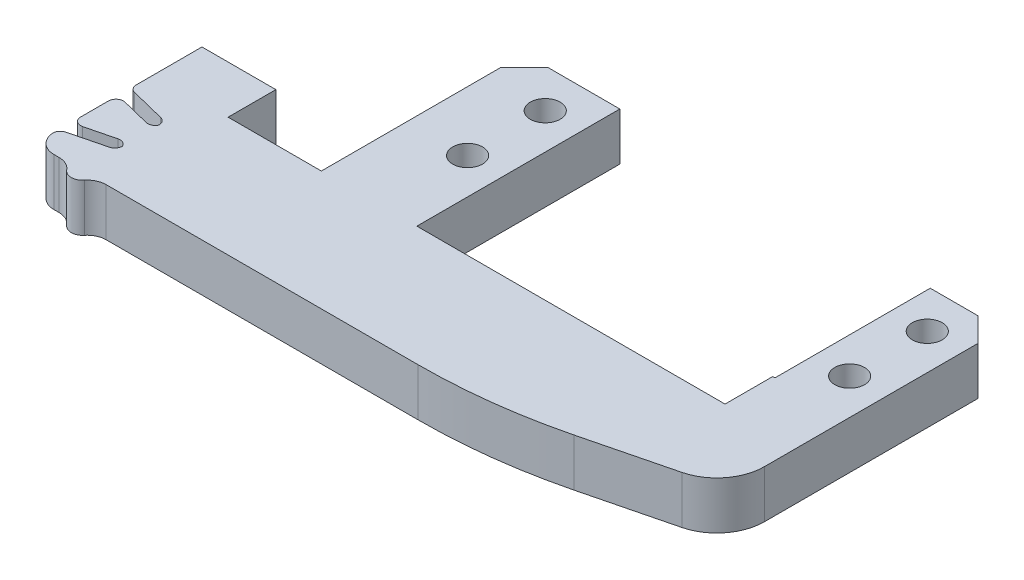
SolidWorks part; units mm, degrees
ref_plane "Front Plane" through (0, 0, 0) normal (0, 0, 1) x (1, 0, 0)
ref_plane "Top Plane" through (0, 0, 0) normal (0, 1, 0) x (1, 0, 0)
ref_plane "Right Plane" through (0, 0, 0) normal (1, 0, 0) x (0, 0, -1)
sketch "Sketch2" plane through (0, 0, 0) normal (0, 0, 1) x (1, 0, 0)
  line L0 (-33.925, 56.4924) -> (-33.925, -23.0187) construction
  line L1 (48.625, -23.0187) -> (-33.925, -23.0187)
  line L3 (48.625, -29.3687) -> (-33.925, -29.3687)
  line L4 (-33.925, -23.0187) -> (-33.925, -29.3687)
  line L6 (48.625, -29.3687) -> (51.8, -29.3687)
  line L8 (48.625, -23.0187) -> (51.8, -23.0187)
  line L9 (51.8, -29.3687) -> (51.8, -23.0187)
  dimension "D1" = 3.175
extrude "Boss-Extrude1" add sketch "Sketch2" along normal blind 15.875
sketch "Sketch3" plane through (0, 0, 0) normal (0, 0, -1) x (-1, 0, 0)
  line L0 (-51.8, -23.0187) -> (33.925, -23.0187) construction
  line L1 (11.7, -23.0187) -> (-1, -23.0187)
  line L2 (11.7, -23.0187) -> (11.7, -29.3687)
  line L3 (11.7, -29.3687) -> (-1, -29.3687)
  line L4 (-1, -23.0187) -> (-1, -29.3687)
  line L5 (11.7, -23.0187) -> (11.7, -29.3687) construction
  line L6 (33.925, -29.3687) -> (-51.8, -29.3687) construction
  line L7 (-1, -1.3969) -> (-1, -29.3687) construction
  line L10 (-51.8, -23.0187) -> (33.925, -23.0187) construction
  line L11 (-51.8, -29.3687) -> (-41.975, -29.3688)
  line L12 (-51.8, -29.3687) -> (-51.8, -23.0187)
  line L13 (-51.8, -23.0187) -> (-41.975, -23.0187)
  line L14 (-41.975, -29.3688) -> (-41.975, -23.0187)
  dimension "D1" = 9.825
extrude "Boss-Extrude2" add sketch "Sketch3" along normal up to surface (26.9875 mm away)
sketch "Sketch5" plane through (0, -23.0187, 0) normal (0, 1, 0) x (1, 0, 0)
  line L0 (51.8, -15.875) -> (-33.925, -15.875) construction
  line L2 (-33.925, -15.875) -> (-33.925, 0) construction
  circle A0 centre (-27.575, -15.875) radius 1.5
  dimension "D1" = 3
  dimension "D2" = 6.35
extrude "Boss-Extrude4" add sketch "Sketch5" against normal blind 6.35
fillet "Fillet1" radius 2.54 1 edges at (-26.075, -26.1937, 15.875)
sketch "Sketch6" plane through (0, -23.0187, 0) normal (0, 1, 0) x (1, 0, 0)
  line L0 (-33.925, -7.9375) -> (48.625, -7.9375) construction
  line L1 (-33.925, -15.875) -> (-33.925, 0) construction
  line L2 (-33.925, -12.7) -> (-33.925, -3.175) construction
  line L3 (-27.575, -11.1125) -> (-27.575, -4.7625) construction
  line L4 (-33.925, -3.175) -> (-27.575, -4.7625)
  line L5 (-34.31, -4.7151) -> (-27.96, -6.3026)
  line L6 (-33.925, -12.7) -> (-27.575, -11.1125)
  line L7 (-34.31, -11.1599) -> (-27.96, -9.5724)
  line L8 (-27.96, -6.3026) -> (-27.575, -4.7625)
  line L9 (-34.31, -4.7151) -> (-33.925, -3.175)
  line L10 (-33.925, -12.7) -> (-34.31, -11.1599)
  line L11 (-27.575, -11.1125) -> (-27.96, -9.5724)
  point P7 (-33.925, -7.9375)
  point P10 (-27.575, -7.9375)
  dimension "D1" = 9.525
  dimension "D2" = 6.35
  dimension "D3" = 6.35
  dimension "D4" = 1.5875
extrude "Cut-Extrude1" cut sketch "Sketch6" against normal through all
fillet "Fillet3" radius 1 8 edges at (-27.575, -26.1938, 11.1125) (-27.96, -26.1938, 9.5724) (-27.96, -26.1938, 6.3026) (-27.575, -26.1938, 4.7625) (-33.925, -26.1938, 3.175) (-33.925, -26.1938, 4.8114) (-33.925, -26.1938, 11.0636) (-33.925, -26.1938, 12.7)
sketch "Sketch7" plane through (0, -29.3688, 0) normal (0, -1, 0) x (-1, 0, 0)
  line L0 (-51.8, -15.875) -> (-51.8, -9.525)
  line L1 (-51.8, -15.875) -> (-51.8, 26.9875) construction
  line L2 (-51.8, -9.525) -> (-26.4, -15.875)
  line L3 (24.4333, -15.875) -> (-51.8, -15.875) construction
  line L4 (-26.4, -15.875) -> (-51.8, -15.875)
  dimension "D1" = 6.35
  dimension "D2" = 25.4
extrude "Cut-Extrude2" cut sketch "Sketch7" against normal blind 6.35
fillet "Fillet4" radius 6.35 1 edges at (51.8, -26.1937, 9.525)
fillet "Fillet5" radius 76.2 1 edges at (26.4, -26.1938, 15.875)
sketch "Sketch8" plane through (0, 0, 0) normal (0, 0, -1) x (-1, 0, 0)
  line L0 (11.7, -23.0187) -> (33.925, -23.0187) construction
  line L1 (33.925, -29.3687) -> (24.1, -29.3687)
  line L2 (33.925, -29.3687) -> (33.925, -23.0187)
  line L3 (33.925, -23.0187) -> (24.1, -23.0187)
  line L4 (24.1, -29.3687) -> (24.1, -23.0187)
  dimension "D1" = 9.825
extrude "Boss-Extrude5" add sketch "Sketch8" along normal blind 6.35
sketch "Sketch9" plane through (0, -23.0187, 0) normal (0, 1, 0) x (1, 0, 0)
  line L0 (41.975, 0) -> (1, 0) construction
  line L1 (41.975, 26.9875) -> (42.275, 26.9875)
  line L2 (41.975, 26.9875) -> (41.975, 6.35)
  line L3 (41.975, 6.35) -> (42.275, 6.35)
  line L4 (42.275, 26.9875) -> (42.275, 6.35)
  dimension "D1" = 0.3
  dimension "D2" = 6.35
extrude "Cut-Extrude3" cut sketch "Sketch9" against normal through all
fillet "Fillet6" radius 2.54 1 edges at (-29.075, -26.1937, 15.875)
fillet "Fillet7" radius 2.54 1 edges at (-33.925, -26.1937, 15.875)
sketch "Sketch10" plane through (0, -29.3688, 0) normal (0, -1, 0) x (-1, 0, 0)
  circle A0 centre (-47.0375, 21.8281) radius 1.9844
  circle A1 centre (-47.0375, 11.5094) radius 1.9844
  circle A2 centre (3.7625, 11.5094) radius 1.9844
  circle A3 centre (3.7625, 21.8281) radius 1.9844
extrude "Cut-Extrude4" cut sketch "Sketch10" against normal through all
chamfer "Chamfer1" distance 3.175 angle 45 2 edges at (51.8, -26.1937, -26.9875) (-11.7, -26.1937, -26.9875)
